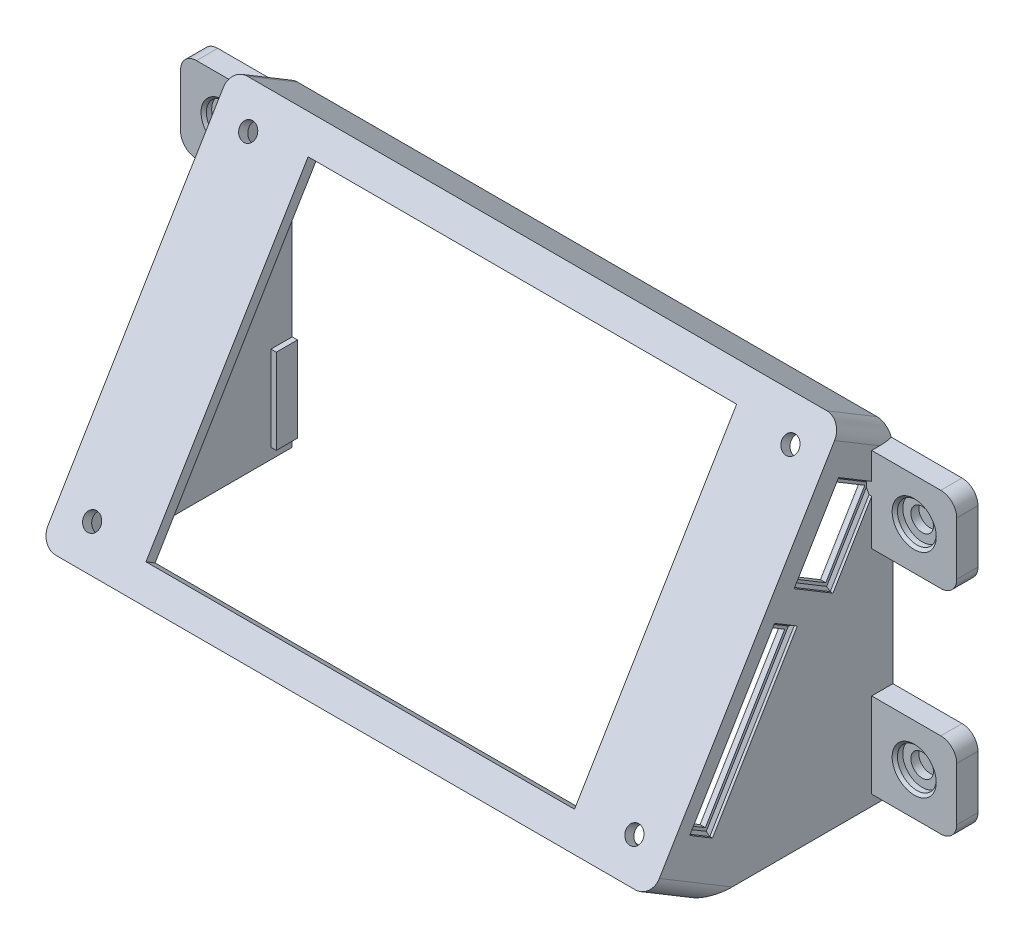
SolidWorks part; units mm, degrees
ref_plane "Front Plane" through (0, 0, 0) normal (0, 0, 1) x (1, 0, 0)
ref_plane "Top Plane" through (0, 0, 0) normal (0, 1, 0) x (1, 0, 0)
ref_plane "Right Plane" through (0, 0, 0) normal (1, 0, 0) x (0, 0, -1)
sketch "Sketch1" plane through (0, 0, 0) normal (1, 0, 0) x (0, 0, -1)
  line L0 (0, 0) -> (0, 60)
  line L1 (0, 60) -> (-36.0555, 0)
  line L2 (-36.0555, 0) -> (0, 0)
  dimension "D1" = 60
  dimension "D2" = 70
extrude "Boss-Extrude1" add sketch "Sketch1" along normal blind 115
sketch "Sketch2" plane through (0, 15.9184, 26.4898) normal (0, 0.5151, 0.8571) x (1, 0, 0)
  line L1 (0, 51.4286) -> (115, 51.4286)
  line L2 (0, 51.4286) -> (0, -18.5714)
  line L3 (0, -18.5714) -> (115, -18.5714)
  line L4 (115, 51.4286) -> (115, -18.5714)
extrude "Boss-Extrude2" add sketch "Sketch2" along normal blind 11
fillet "Fillet1" radius 3 4 edges at (0, 2.8329, 40.7698) (0, 62.8329, 4.7143) (115, 2.8329, 40.7698) (115, 62.8329, 4.7143)
shell "Shell1" thickness 2 removed face at (57.5, 0, 22.4976) removed face at (57.5, 39.075, 0)
sketch "Sketch3" plane through (0, 21.5842, 35.9183) normal (0, 0.5151, 0.8571) x (1, 0, 0)
  line L0 (0, 48.4286) -> (0, -15.5714) construction
  line L1 (112, 51.4286) -> (3, 51.4286) construction
  line L2 (115, -15.5714) -> (115, 48.4286) construction
  line L3 (3, -18.5714) -> (112, -18.5714) construction
  circle A0 centre (6.5, 44.9286) radius 1.6
  circle A1 centre (6.5, -12.0714) radius 1.6
  circle A2 centre (108.5, -12.0714) radius 1.6
  circle A3 centre (108.5, 44.9286) radius 1.6
  dimension "D1" = 3.2
  dimension "D2" = 6.5
  dimension "D3" = 6.5
  dimension "D4" = 6.5
  dimension "D5" = 6.5
extrude "Cut-Extrude1" cut sketch "Sketch3" against normal up to surface (2 mm away) up to face at (57.5, 34.6357, 25.742)
sketch "Sketch4" plane through (0, 21.5842, 35.9183) normal (0, 0.5151, 0.8571) x (1, 0, 0)
  line L0 (112, 51.4286) -> (3, 51.4286) construction
  line L1 (17.2, 46.0286) -> (97.8, 46.0286)
  line L2 (17.2, 46.0286) -> (17.2, -13.1714)
  line L3 (17.2, -13.1714) -> (97.8, -13.1714)
  line L4 (97.8, 46.0286) -> (97.8, -13.1714)
  line L5 (0, 48.4286) -> (0, -15.5714) construction
  dimension "D1" = 59.2
  dimension "D2" = 80.6
  dimension "D3" = 5.4
  dimension "D4" = 17.2
extrude "Cut-Extrude2" cut sketch "Sketch4" against normal up to surface (2 mm away) up to face at (108.5, 57.6929, 11.8864)
sketch "Sketch5" plane through (115, 0, 0) normal (1, 0, 0) x (0, 0, -1)
  line L0 (-36.8615, 12.7343) -> (-34.29, 11.1891)
  line L1 (-34.29, 11.1891) -> (-19.3528, 36.0462)
  line L2 (-19.3528, 36.0462) -> (-21.9242, 37.5915)
  line L3 (-21.9242, 37.5915) -> (-36.8615, 12.7343)
  line L4 (-43.9388, 8.2373) -> (-10.9738, 63.0944) construction
  line L5 (-36.0555, 0) -> (-45.4841, 5.6659) construction
  line L6 (-17.2077, 43.1105) -> (-9.8729, 55.3162)
  line L7 (-9.8729, 55.3162) -> (-4.3015, 51.9682)
  line L8 (-4.3015, 51.9682) -> (-11.6362, 39.7625)
  line L9 (-11.6362, 39.7625) -> (-17.2077, 43.1105)
  line L10 (0, 56.5) -> (-10.9738, 63.0944) construction
  line L11 (-9.4286, 65.6659) -> (0, 60) construction
  dimension "D1" = 3
  dimension "D2" = 29
  dimension "D3" = 10.5
  dimension "D4" = 3.75
  dimension "D5" = 9.1
  dimension "D6" = 4.95
  dimension "D7" = 6.5
  dimension "D8" = 14.24
extrude "Cut-Extrude3" cut sketch "Sketch5" against normal up to surface (2 mm away) up to face at (113, 25.1543, 16.343)
sketch "Sketch6" plane through (115, 0, 0) normal (1, 0, 0) x (0, 0, -1)
  line L8 (-38.2337, 12.3923) -> (-33.948, 9.8169)
  line L9 (-33.948, 9.8169) -> (-17.9805, 36.3883)
  line L10 (-17.9805, 36.3883) -> (-22.2663, 38.9637)
  line L11 (-22.2663, 38.9637) -> (-38.2337, 12.3923)
  line L12 (-38.2337, 12.3923) -> (-33.948, 9.8169)
  line L13 (-33.948, 9.8169) -> (-17.9805, 36.3883)
  line L14 (-17.9805, 36.3883) -> (-22.2663, 38.9637)
  line L15 (-22.2663, 38.9637) -> (-38.2337, 12.3923)
  line L20 (-11.2942, 38.3903) -> (-2.9293, 52.3103)
  line L21 (-2.9293, 52.3103) -> (-10.215, 56.6884)
  line L22 (-10.215, 56.6884) -> (-18.5799, 42.7684)
  line L23 (-18.5799, 42.7684) -> (-11.2942, 38.3903)
  line L24 (-11.2942, 38.3903) -> (-2.9293, 52.3103)
  line L25 (-2.9293, 52.3103) -> (-10.215, 56.6884)
  line L26 (-10.215, 56.6884) -> (-18.5799, 42.7684)
  line L27 (-18.5799, 42.7684) -> (-11.2942, 38.3903)
  dimension "D1" = 1
  dimension "D2" = 1
extrude "Cut-Extrude4" cut sketch "Sketch6" against normal blind 1
ref_plane "Plane1" through (58, 0, 0) normal (1, 0, 0) x (0, 0, -1)
chamfer "Chamfer3" distance 0.5 angle 45 8 edges at (114, 37.676, 20.1234) (114, 23.1026, 25.9643) (114, 25.678, 30.25) (114, 11.1046, 36.0908) (114, 40.5794, 14.937) (114, 49.7284, 14.3974) (114, 54.4994, 6.5721) (114, 45.3503, 7.1117)
sketch "Sketch7" plane through (115, 0, 0) normal (1, 0, 0) x (0, 0, -1)
  line L0 (0, 0) -> (0, 56.5) construction
  line L1 (0, 58) -> (-4, 58)
  line L2 (0, 58) -> (0, 42)
  line L3 (0, 42) -> (-4, 42)
  line L4 (-4, 58) -> (-4, 42)
  line L5 (-30.2312, 0) -> (0, 0) construction
  line L6 (0, 18) -> (-4, 18)
  line L7 (0, 18) -> (0, 2)
  line L8 (0, 2) -> (-4, 2)
  line L9 (-4, 18) -> (-4, 2)
  dimension "D1" = 16
  dimension "D2" = 2
  dimension "D3" = 24
  dimension "D4" = 4
extrude "Boss-Extrude3" add sketch "Sketch7" along normal blind 16 and the other way blind 2
sketch "Sketch8" plane through (0, 0, 4) normal (0, 0, 1) x (1, 0, 0)
  line L0 (123, 58) -> (123, 42) construction
  line L1 (115, 58) -> (131, 58) construction
  line L2 (115, 42) -> (131, 42) construction
  line L3 (123, 18) -> (123, 2) construction
  line L4 (115, 18) -> (131, 18) construction
  line L5 (115, 2) -> (131, 2) construction
  circle A0 centre (123, 50) radius 2.125
  circle A1 centre (123, 10) radius 2.125
  dimension "D1" = 4.25
extrude "Cut-Extrude5" cut sketch "Sketch8" against normal blind 3
sketch "Sketch9" plane through (0, 0, 4) normal (0, 0, 1) x (1, 0, 0)
  circle A0 centre (123, 50) radius 3.65
  circle A1 centre (123, 10) radius 3.65
  dimension "D1" = 7.3
extrude "Cut-Extrude6" cut sketch "Sketch9" against normal blind 1.5
chamfer "Chamfer4" distance 0.5 angle 45 2 edges at (126.65, 10, 4) (126.65, 50, 4)
fillet "Fillet2" radius 3 4 edges at (131, 18, 2) (131, 2, 2) (131, 58, 2) (131, 42, 2)
mirror "Mirror1" about plane through (58, 0, 0) normal (1, 0, 0) of "Fillet2", "Chamfer4", "Cut-Extrude6", "Cut-Extrude5", "Boss-Extrude3"
